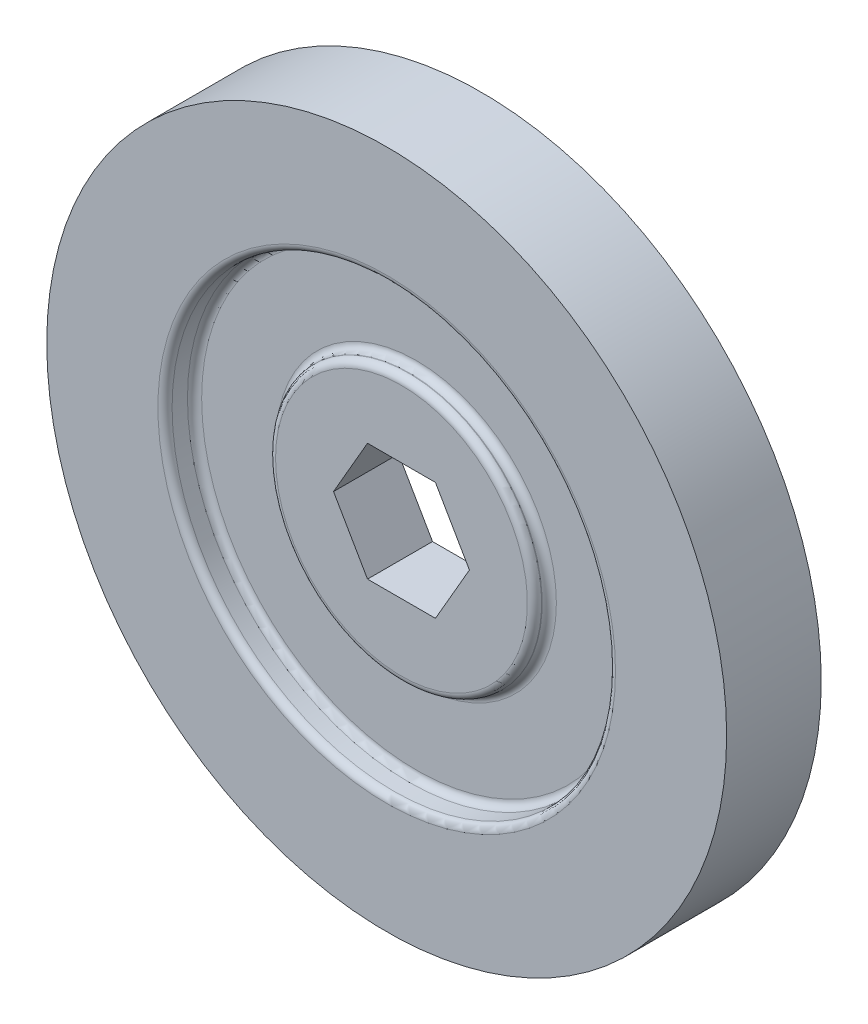
SolidWorks part; units mm, degrees
ref_plane "Front Plane" through (0, 0, 0) normal (0, 0, 1) x (1, 0, 0)
ref_plane "Top Plane" through (0, 0, 0) normal (0, 1, 0) x (1, 0, 0)
ref_plane "Right Plane" through (0, 0, 0) normal (1, 0, 0) x (0, 0, -1)
sketch "Sketch1" plane through (0, 0, 0) normal (0, 0, 1) x (1, 0, 0)
  circle A0 centre (0, 0) radius 36.5125
  dimension "D1" = 73.025
extrude "Boss-Extrude1" add sketch "Sketch1" along normal blind 5.08 and the other way blind 5.08
sketch "Sketch2" plane through (0, 0, 5.08) normal (0, 0, 1) x (1, 0, 0)
  line L1 (3.6489, 6.32) -> (-3.6489, 6.32)
  line L2 (-3.6489, 6.32) -> (-7.2977, 0)
  line L3 (-7.2977, 0) -> (-3.6489, -6.32)
  line L4 (-3.6489, -6.32) -> (3.6489, -6.32)
  line L5 (3.6489, -6.32) -> (7.2977, 0)
  line L6 (7.2977, 0) -> (3.6489, 6.32)
  circle A0 centre (0, 0) radius 6.32 construction
  dimension "D1" = 12.64
extrude "Cut-Extrude1" cut sketch "Sketch2" against normal through all
sketch "Sketch3" plane through (0, 0, 0) normal (1, 0, 0) x (0, 0, -1)
  line L0 (3.4925, 14.2875) -> (1.905, 14.2875)
  line L1 (5.08, -36.5125) -> (5.08, 36.5125) construction
  line L2 (1.905, 14.2875) -> (1.905, 23.8125)
  line L3 (1.905, 23.8125) -> (5.08, 23.8125)
  line L4 (5.08, 23.8125) -> (5.08, 0)
  line L5 (22.753, 0) -> (-27.7028, 0) construction
  line L6 (5.08, 36.5125) -> (-5.08, 36.5125) construction
  line L7 (5.08, 0) -> (3.4925, 0)
  line L8 (3.4925, 0) -> (3.4925, 14.2875)
  dimension "D1" = 9.525
  dimension "D2" = 12.7
  dimension "D3" = 1.5875
  dimension "D4" = 3.175
revolve "Cut-Revolve1" cut sketch "Sketch3" angle 360 about L5
fillet "Fillet1" radius 0.762 3 edges at (-14.2875, 0, -1.905) (-23.8125, 0, -5.08) (-14.2875, 0, -3.4925)
mirror "Mirror1" about plane through (0, 0, 0) normal (0, 0, 1) of "Cut-Revolve1"
fillet "Fillet2" radius 0.762 4 edges at (-23.8125, 0, 5.08) (-23.8125, 0, 1.905) (-14.2875, 0, 1.905) (-14.2875, 0, 3.4925)
